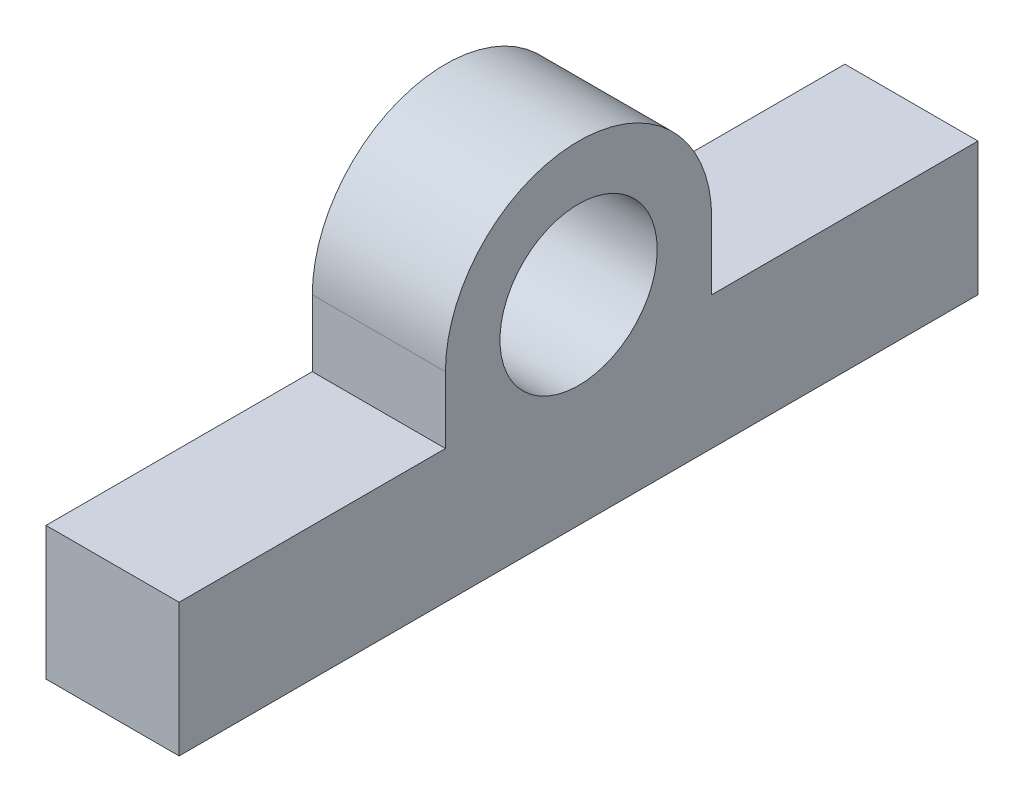
SolidWorks part; units mm, degrees
ref_plane "Front Plane" through (0, 0, 0) normal (0, 0, 1) x (1, 0, 0)
ref_plane "Top Plane" through (0, 0, 0) normal (0, 1, 0) x (1, 0, 0)
ref_plane "Right Plane" through (0, 0, 0) normal (1, 0, 0) x (0, 0, -1)
sketch "Sketch1" plane through (0, 0, 0) normal (1, 0, 0) x (0, 0, -1)
  line L0 (0, 0) -> (76.2, 0)
  line L1 (76.2, 0) -> (76.2, 12.7)
  line L2 (76.2, 12.7) -> (50.8, 12.7)
  line L3 (0, 12.7) -> (0, 0)
  line L5 (50.8, 12.7) -> (50.8, 19.05)
  line L7 (25.4, 19.05) -> (25.4, 12.7)
  line L9 (25.4, 12.7) -> (0, 12.7)
  arc A0 (50.8, 19.05) -> (25.4, 19.05) centre (38.1, 19.05) ccw
  dimension "D1" = 76.2
  dimension "D2" = 12.7
  dimension "D3" = 25.4
  dimension "D4" = 25.4
  dimension "D5" = 6.35
extrude "Boss-Extrude1" add sketch "Sketch1" along normal blind 12.7
sketch "Sketch2" plane through (12.7, 0, 0) normal (1, 0, 0) x (0, 0, -1)
  circle A0 centre (38.1, 19.05) radius 7.5
  dimension "D1" = 15
extrude "Cut-Extrude1" cut sketch "Sketch2" against normal through all
sketch "Sketch3" plane through (0, 0, 0) normal (0, -1, 0) x (1, 0, 0)
  line L0 (12.7, -76.2) -> (0, -76.2) construction
  line L3 (12.7, 0) -> (0, 0) construction
  circle A0 centre (6.35, -12.7) radius 2
  circle A1 centre (6.35, -63.5) radius 2
  point P4 (6.35, 0)
  point P10 (6.35, -76.2)
  dimension "D1" = 4
  dimension "D4" = 4
  dimension "D6" = 12.7
  dimension "D2" = 0
  dimension "D3" = 12.7
  dimension "D5" = 0
  dimension "D7" = 50.8
extrude "Cut-Extrude2" cut sketch "Sketch3" against normal blind 7
equation "\"bearing_d\"= 0.5in"
equation "\"heat_set_d\"= 0.1in"
